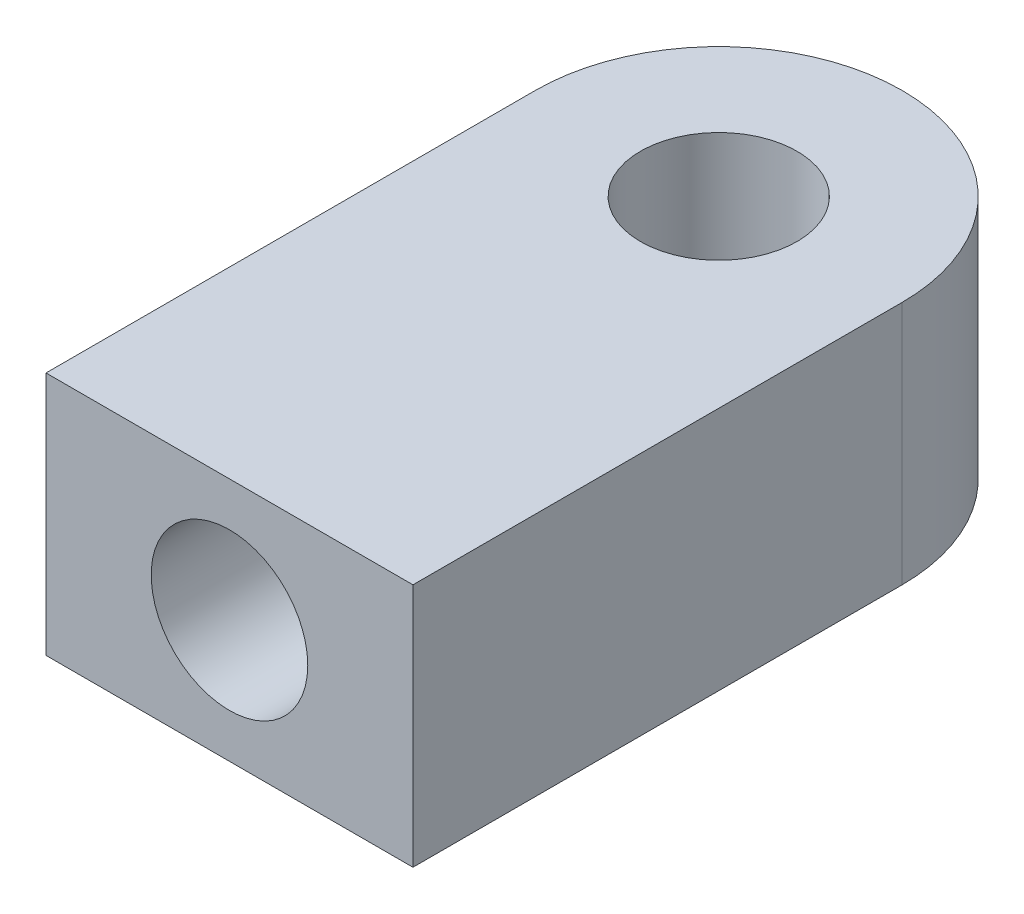
SolidWorks part; units mm, degrees
ref_plane "Front Plane" through (0, 0, 0) normal (0, 0, 1) x (1, 0, 0)
ref_plane "Top Plane" through (0, 0, 0) normal (0, 1, 0) x (1, 0, 0)
ref_plane "Right Plane" through (0, 0, 0) normal (1, 0, 0) x (0, 0, -1)
sketch "Sketch1" plane through (0, 0, 0) normal (0, 1, 0) x (1, 0, 0)
  line L0 (0, 0) -> (0, 12.7)
  line L1 (9.525, 12.7) -> (9.525, 0)
  line L2 (9.525, 0) -> (0, 0)
  arc A0 (0, 12.7) -> (9.525, 12.7) centre (4.7625, 12.7) cw
  circle A1 centre (4.7625, 12.7) radius 2.032
  dimension "D3" = 4.064
  dimension "D1" = 9.525
  dimension "D2" = 12.7
extrude "Boss-Extrude1" add sketch "Sketch1" along normal blind 6.35
sketch "Sketch2" plane through (0, 0, 0) normal (0, 0, 1) x (1, 0, 0)
  line L1 (0, 6.35) -> (9.525, 6.35) construction
  line L2 (0, 6.35) -> (0, 0) construction
  circle A0 centre (4.7625, 3.175) radius 2.032
  point P4 (4.7625, 6.35)
  point P7 (0, 3.175)
  dimension "D1" = 4.064
extrude "Cut-Extrude1" cut sketch "Sketch2" against normal blind 9.525
